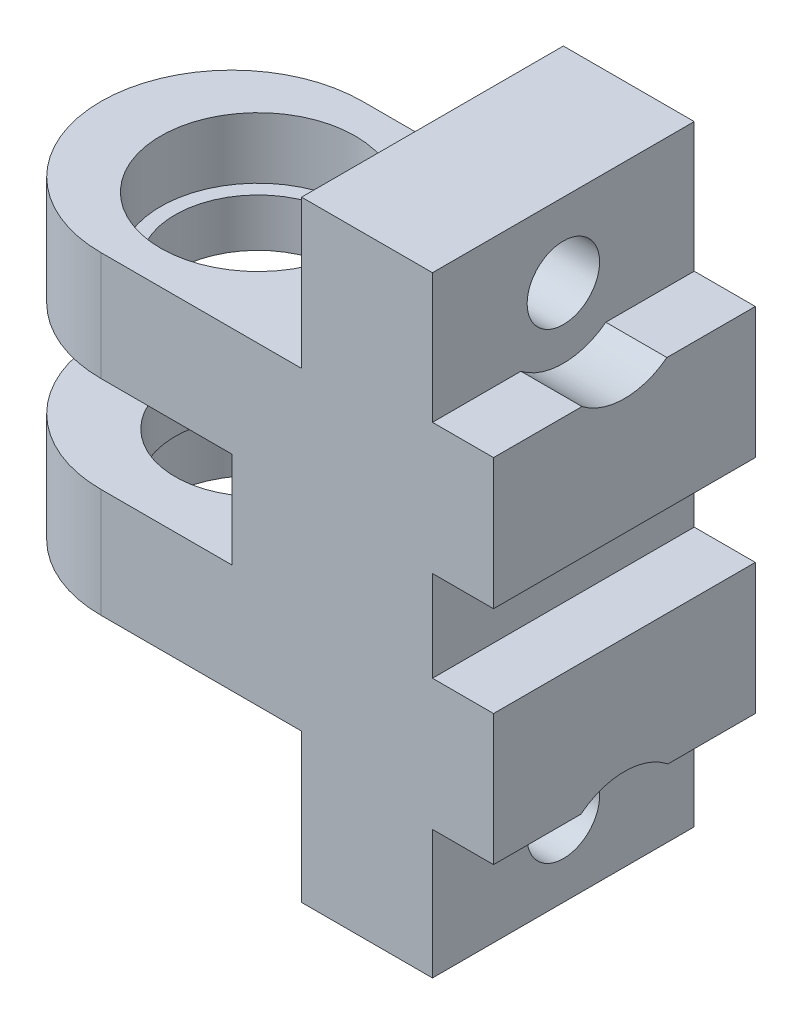
SolidWorks part; units mm, degrees
ref_plane "Спереди" through (0, 0, 0) normal (0, 0, 1) x (1, 0, 0)
ref_plane "Сверху" through (0, 0, 0) normal (0, 1, 0) x (1, 0, 0)
ref_plane "Справа" through (0, 0, 0) normal (1, 0, 0) x (0, 0, -1)
sketch "Sketch1" plane through (0, 0, 0) normal (0, 1, 0) x (1, 0, 0)
  line L1 (21.5, -15) -> (-21.5, -15)
  line L2 (21.5, -15) -> (21.5, 15)
  line L3 (21.5, 15) -> (-21.5, 15)
  line L4 (-21.5, -15) -> (-21.5, 15)
  line L5 (21.5, -15) -> (-21.5, 15) construction
  line L6 (21.5, 15) -> (-21.5, -15) construction
  point P0 (0, 0)
  dimension "D1" = 43
  dimension "D2" = 30
extrude "Boss-Extrude1" add sketch "Sketch1" along normal blind 36
sketch "Sketch2" plane through (-21.5, 0, 0) normal (-1, 0, 0) x (0, 0, 1)
  line L0 (0, 36) -> (0, 0) construction
  line L1 (-15, 36) -> (15, 36) construction
  line L2 (-15, 0) -> (15, 0) construction
  line L3 (-15, 36) -> (-15, 0) construction
  line L4 (15, 12.5) -> (-15, 12.5)
  line L5 (15, 12.5) -> (15, 23.5)
  line L6 (15, 23.5) -> (-15, 23.5)
  line L7 (-15, 12.5) -> (-15, 23.5)
  line L8 (15, 12.5) -> (-15, 23.5) construction
  line L9 (15, 23.5) -> (-15, 12.5) construction
  point P6 (0, 18)
  dimension "D1" = 11
extrude "Cut-Extrude1" cut sketch "Sketch2" against normal blind 30
sketch "Sketch3" plane through (0, 36, 0) normal (0, 1, 0) x (1, 0, 0)
  line L0 (-21.5, 0) -> (21.5, 0) construction
  line L1 (-21.5, 15) -> (-21.5, -15) construction
  line L2 (21.5, -15) -> (21.5, 15) construction
  circle A0 centre (-3.5, 0) radius 11.15
  dimension "D1" = 22.3
  dimension "D2" = 18
extrude "Cut-Extrude2" cut sketch "Sketch3" against normal blind 7
sketch "Sketch4" plane through (0, 0, 0) normal (0, -1, 0) x (1, 0, 0)
  line L0 (-21.5, 0) -> (21.5, 0) construction
  line L1 (-21.5, -15) -> (-21.5, 15) construction
  line L2 (21.5, 15) -> (21.5, -15) construction
  circle A0 centre (-3.5, 0) radius 11.15
  dimension "D1" = 22.3
  dimension "D2" = 18
extrude "Cut-Extrude3" cut sketch "Sketch4" against normal blind 7
sketch "Sketch5" plane through (0, 29, 0) normal (0, 1, 0) x (1, 0, 0)
  circle A0 centre (-3.5, 0) radius 9.5
  dimension "D1" = 19
extrude "Cut-Extrude4" cut sketch "Sketch5" against normal through all
fillet "Fillet2" radius 15 4 edges at (-21.5, 6.25, -15) (-21.5, 6.25, 15) (-21.5, 29.75, 15) (-21.5, 29.75, -15)
sketch "Sketch6" plane through (21.5, 0, 0) normal (1, 0, 0) x (0, 0, -1)
  line L0 (15, 18) -> (-15, 18) construction
  line L1 (15, 36) -> (15, 0) construction
  line L2 (-15, 36) -> (-15, 0) construction
  line L4 (-15, 53) -> (15, 53)
  line L5 (-15, 53) -> (-15, -17)
  line L6 (-15, -17) -> (15, -17)
  line L7 (15, 53) -> (15, -17)
  line L8 (-15, 53) -> (15, -17) construction
  line L9 (-15, -17) -> (15, 53) construction
  point P6 (0, 18)
  dimension "D1" = 30
  dimension "D2" = 70
extrude "Boss-Extrude2" add sketch "Sketch6" along normal blind 10
sketch "Sketch7" plane through (31.5, 0, 0) normal (1, 0, 0) x (0, 0, -1)
  line L0 (0, 53) -> (0, -17) construction
  line L1 (15, 53) -> (-15, 53) construction
  line L2 (-15, -17) -> (15, -17) construction
  line L3 (15, -17) -> (15, 53) construction
  line L4 (-15, 23.15) -> (15, 23.15)
  line L5 (-15, 23.15) -> (-15, 38.15)
  line L6 (-15, 38.15) -> (15, 38.15)
  line L7 (15, 23.15) -> (15, 38.15)
  line L8 (-15, 23.15) -> (15, 38.15) construction
  line L9 (-15, 38.15) -> (15, 23.15) construction
  line L11 (-15, 12.75) -> (15, 12.75)
  line L12 (-15, 12.75) -> (-15, -2.25)
  line L13 (-15, -2.25) -> (15, -2.25)
  line L14 (15, 12.75) -> (15, -2.25)
  line L15 (-15, 12.75) -> (15, -2.25) construction
  line L16 (-15, -2.25) -> (15, 12.75) construction
  point P6 (0, 30.65)
  point P13 (0, 5.25)
  point P18 (0, 18)
  dimension "D1" = 10.4
  dimension "D2" = 15
  dimension "D3" = 5.15
extrude "Boss-Extrude3" add sketch "Sketch7" along normal blind 7
sketch "Sketch8" plane through (21.5, 0, 0) normal (-1, 0, 0) x (0, 0, 1)
  line L0 (0, 36) -> (0, 53) construction
  line L1 (15, 36) -> (-15, 36) construction
  line L2 (-15, 53) -> (15, 53) construction
  line L5 (0, 0) -> (0, -17) construction
  line L6 (15, 0) -> (-15, 0) construction
  line L7 (15, -17) -> (-15, -17) construction
  circle A0 centre (0, -8.5) radius 4.15
  circle A1 centre (0, 44.5) radius 4.15
  dimension "D1" = 8.3
extrude "Cut-Extrude5" cut sketch "Sketch8" against normal through all
sketch "Sketch9" plane through (31.5, 0, 0) normal (1, 0, 0) x (0, 0, -1)
  circle A0 centre (0, -8.5) radius 8
  circle A1 centre (0, 44.5) radius 8
  dimension "D1" = 16
extrude "Cut-Extrude6" cut sketch "Sketch9" along normal through all
sketch "Sketch10" plane through (21.5, 0, 0) normal (-1, 0, 0) x (0, 0, 1)
  line L1 (-15, 0) -> (15, 0)
  line L2 (-15, 0) -> (-15, -17)
  line L3 (-15, -17) -> (15, -17)
  line L4 (15, 0) -> (15, -17)
  line L5 (-15, 0) -> (15, -17) construction
  line L6 (-15, -17) -> (15, 0) construction
  line L7 (-15, 36) -> (15, 36)
  line L8 (-15, 36) -> (-15, 53)
  line L9 (-15, 53) -> (15, 53)
  line L10 (15, 36) -> (15, 53)
  line L11 (-15, 36) -> (15, 53) construction
  line L12 (-15, 53) -> (15, 36) construction
  circle A0 centre (0, -8.5) radius 4.15
  circle A1 centre (0, 44.5) radius 4.15
  point P0 (0, -8.5)
  point P7 (0, 44.5)
extrude "Boss-Extrude4" add sketch "Sketch10" along normal blind 5
